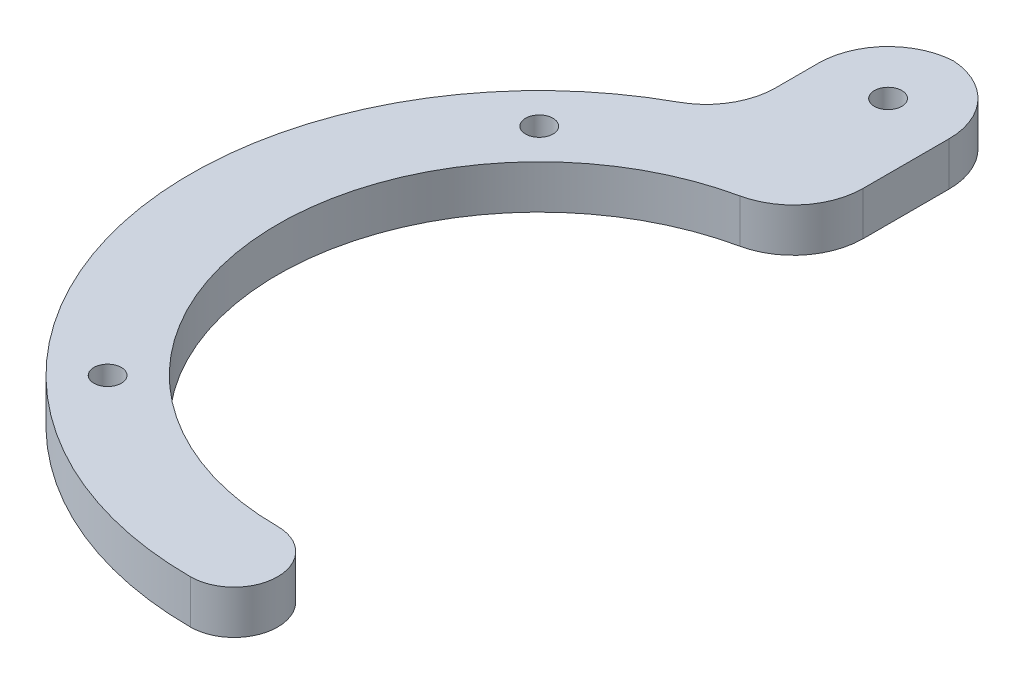
SolidWorks part; units mm, degrees
material "Pine"
ref_plane "Front Plane" through (0, 0, 0) normal (0, 0, 1) x (1, 0, 0)
ref_plane "Top Plane" through (0, 0, 0) normal (0, 1, 0) x (1, 0, 0)
ref_plane "Right Plane" through (0, 0, 0) normal (1, 0, 0) x (0, 0, -1)
sketch "Sketch1" plane through (0, 0, 0) normal (0, 1, 0) x (1, 0, 0)
  line L0 (0, 0) -> (19.05, 0)
  line L1 (19.05, 0) -> (19.05, -19.05)
  line L2 (0, 0) -> (0, -22.7571)
  line L3 (19.05, -19.05) -> (19.05, -120.65) construction
  line L4 (19.05, -31.75) -> (19.05, -19.05)
  line L5 (19.05, -9.525) -> (0, -9.525) construction
  line L6 (19.05, -69.85) -> (-12.3809, -38.4191) construction
  line L7 (19.05, -69.85) -> (-12.3809, -101.2809) construction
  arc A0 (19.05, -19.05) -> (19.05, -120.65) centre (19.05, -69.85) ccw
  arc A1 (19.05, -31.75) -> (19.05, -107.95) centre (19.05, -69.85) ccw
  arc A2 (19.05, -107.95) -> (19.05, -120.65) centre (19.05, -114.3) cw
  circle A3 centre (9.525, -9.525) radius 2
  circle A4 centre (19.05, -69.85) radius 44.45 construction
  circle A5 centre (-12.3809, -38.4191) radius 2
  circle A6 centre (-12.3809, -101.2809) radius 2
  dimension "D2" = 76.2
  dimension "D5" = 4
  dimension "D6" = 88.9
  dimension "D7" = 4
  dimension "D8" = 4
  dimension "D1" = 12.7
  dimension "D3" = 19.05
  dimension "D4" = 19.05
  dimension "D9" = 135
  dimension "D10" = 45
extrude "Boss-Extrude1" add sketch "Sketch1" along normal blind 6.35 contours L3 A1 L4 A0 | A0 L1 L0 L2 | A2 L3 region at (9.525, 0, 0.2968) region at (9.5633, 0, 21.1004) region at (21.745, 0, 114.3)
fillet "Fillet1" radius 10.16 4 edges at (0, 3.175, 22.7571) (19.05, 3.175, 31.75) (0, 3.175, 0) (19.05, 3.175, 0)
equation "\"D6@Sketch1\" = \"D2@Sketch1\" + \"D1@Sketch1\""
